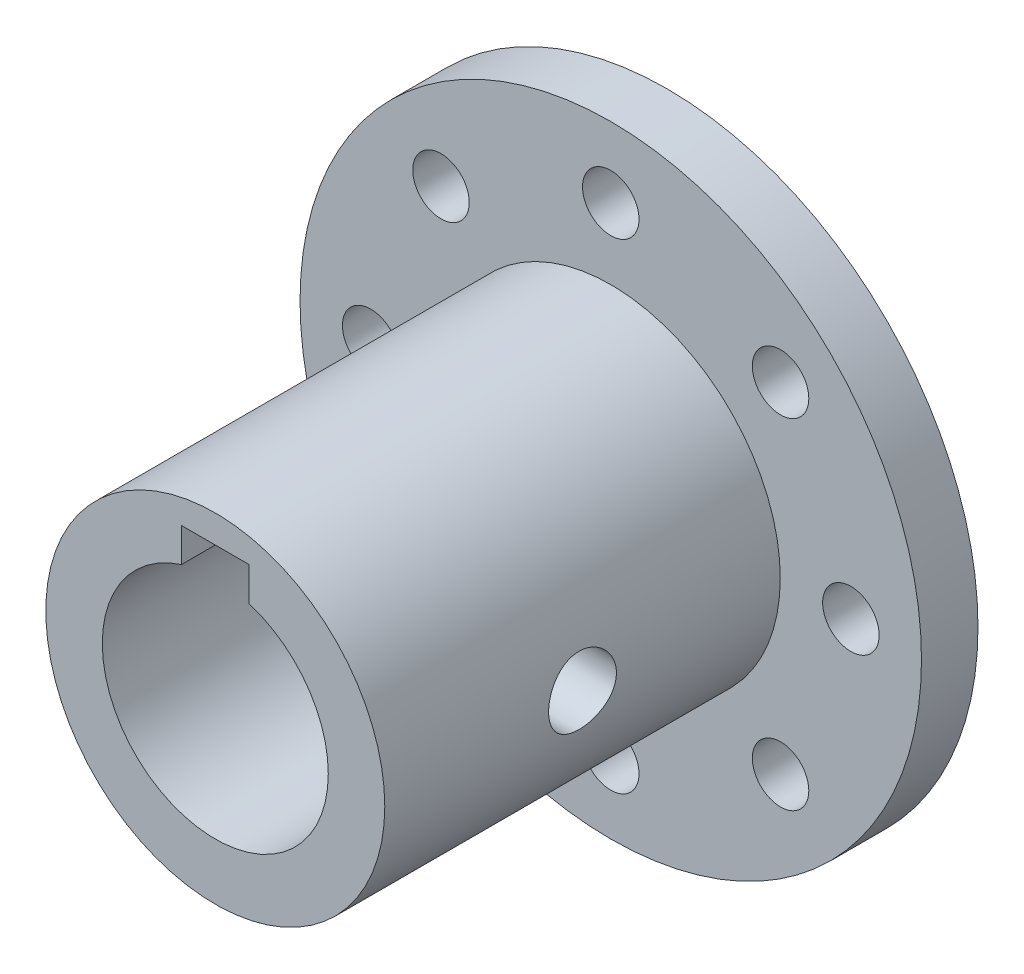
SolidWorks part; units mm, degrees
ref_plane "Alzado" through (0, 0, 0) normal (0, 0, 1) x (1, 0, 0)
ref_plane "Planta" through (0, 0, 0) normal (0, 1, 0) x (1, 0, 0)
ref_plane "Vista lateral" through (0, 0, 0) normal (1, 0, 0) x (0, 0, -1)
sketch "Croquis1" plane through (0, 0, 0) normal (0, 0, 1) x (1, 0, 0)
  circle A0 centre (0, 0) radius 27.5
  dimension "D1" = 55
extrude "Saliente-Extruir1" add sketch "Croquis1" along normal blind 5
sketch "Croquis2" plane through (0, 0, 5) normal (0, 0, 1) x (1, 0, 0)
  circle A0 centre (0, 0) radius 15
  dimension "D1" = 30
extrude "Saliente-Extruir2" add sketch "Croquis2" along normal blind 35
sketch "Croquis3" plane through (0, 0, 40) normal (0, 0, 1) x (1, 0, 0)
  circle A0 centre (0, 0) radius 10
  dimension "D1" = 20
sketch "Croquis5" plane through (0, 0, 5) normal (0, 0, 1) x (1, 0, 0)
  line L0 (0, 21.25) -> (0, -21.25) construction
  line L1 (-21.25, 0) -> (21.25, 0) construction
  line L2 (0, 0) -> (15.026, 15.026) construction
  line L3 (0, 0) -> (-15.026, -15.026) construction
  line L4 (-15.026, 15.026) -> (15.026, -15.026) construction
  circle A0 centre (0, 0) radius 21.25 construction
  circle A2 centre (0, 0) radius 15 construction
  circle A4 centre (0, 21.25) radius 2.5
  circle A5 centre (0, -21.25) radius 2.5
  circle A6 centre (21.25, 0) radius 2.5
  circle A7 centre (-21.25, 0) radius 2.5
  circle A8 centre (15.026, 15.026) radius 2.5
  circle A9 centre (-15.026, 15.026) radius 2.5
  circle A10 centre (-15.026, -15.026) radius 2.5
  circle A11 centre (15.026, -15.026) radius 2.5
  dimension "D1" = 6.25
  dimension "D2" = 45
  dimension "D3" = 5
extrude "Cortar-Extruir4" cut sketch "Croquis5" against normal blind 5
extrude "Cortar-Extruir5" cut sketch "Croquis3" against normal blind 35
sketch "Croquis7" plane through (0, 0, 40) normal (0, 0, 1) x (1, 0, 0)
  line L0 (-3, 12.5394) -> (-3, 9.5394)
  line L1 (0, 12.5394) -> (3, 12.5394)
  line L2 (0, 12.5394) -> (-3, 12.5394)
  line L3 (3, 12.5394) -> (3, 9.5394)
  circle A2 centre (0, 0) radius 10 construction
  circle A3 centre (0, 0) radius 10 construction
  arc A4 (3, 9.5394) -> (-3, 9.5394) centre (0, 0) ccw
  dimension "D1" = 3
  dimension "D2" = 3
  dimension "D3" = 3
  dimension "D4" = 3
extrude "Cortar-Extruir6" cut sketch "Croquis7" against normal blind 32
sketch "Croquis8" plane through (0, 0, 0) normal (0, 0, -1) x (-1, 0, 0)
  circle A0 centre (0, 0) radius 12.5
  circle A1 centre (0, 0) radius 10
  dimension "D1" = 25
  dimension "D2" = 20
extrude "Saliente-Extruir4" add sketch "Croquis8" along normal blind 1
sketch "Croquis9" plane through (0, 0, 0) normal (1, 0, 0) x (0, 0, -1)
  line L0 (-40, 0) -> (1, 0) construction
  line L1 (-40, 15) -> (-40, -15) construction
  line L2 (1, -12.5) -> (1, 12.5) construction
  line L3 (-22.5, 15) -> (-22.5, -15) construction
  line L4 (-5, 15) -> (-40, 15) construction
  line L5 (-40, -15) -> (-5, -15) construction
  circle A1 centre (-22.5, 0) radius 3
  dimension "D1" = 6
extrude "Cortar-Extruir7" cut sketch "Croquis9" against normal mid plane 50
cosmetic thread "Rosca cosmética1" parameters "D2"=7
cosmetic thread "Rosca cosmética2" parameters "D2"=7
hole_wizard "Refrentado para tornillo con cabeza plana de M61" positions "Croquis3D1" profile "Croquis10" counterbore size "M6" standard "DIN" end condition up to next
sketch3d "Croquis3D1"
  circle A0 centre (0, 0, -1) radius 10 construction
  point P5 (0, 0, 0)
  point P10 (0, 0, -11)
sketch "Croquis10" plane through (0, 0, 0) normal (1, 0, 0) x (0, 1, 0)
  line L0 (0, 0) -> (0, 5)
  line L1 (0, 5) -> (3.3, 5)
  line L3 (3.3, 5) -> (3.3, 3.9)
  line L4 (3.3, 3.9) -> (5.5, 3.9)
  line L5 (5.5, 3.9) -> (5.5, 0)
  line L7 (5.5, 0) -> (0, 0)
  line L11 (0, -6.35) -> (0, 107.95) construction
  dimension "Diámetro de taladro hasta el siguiente" = 6.6
  dimension "Profundidad de taladro hasta el siguiente" = 5
  dimension "Diámetro de refrentado" = 11
  dimension "Profundidad de refrentado" = 3.9
